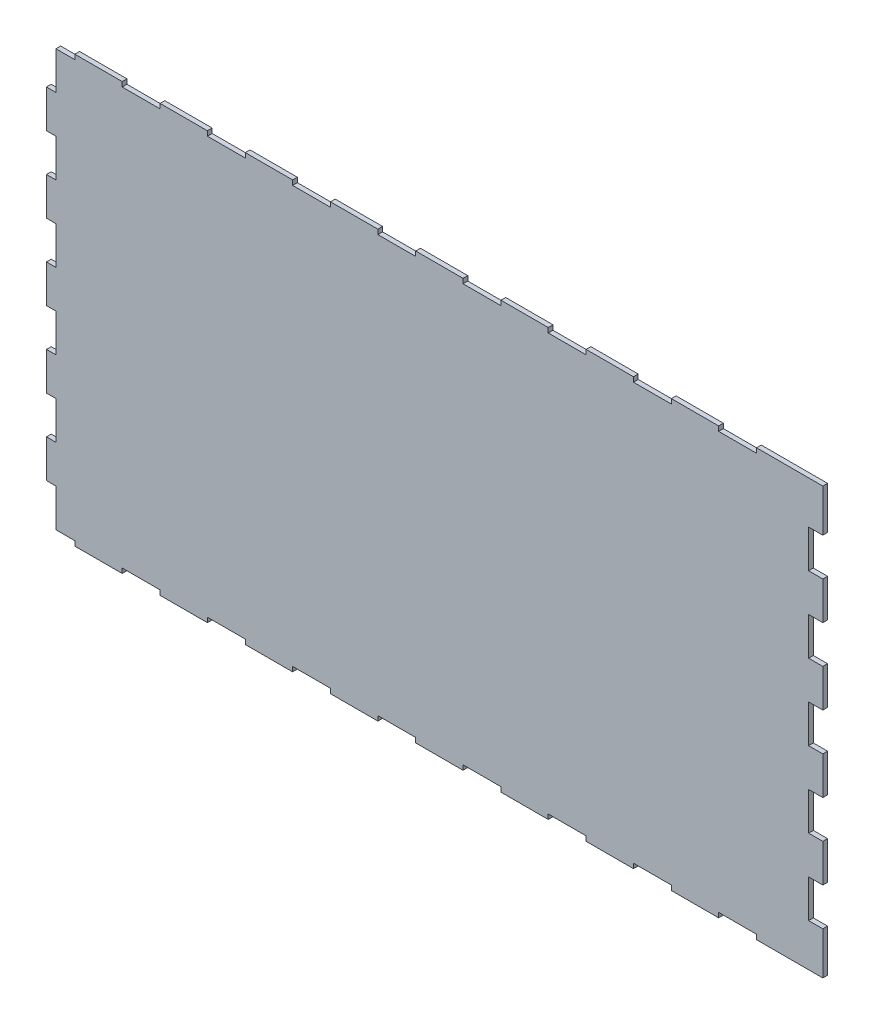
SolidWorks part; units mm, degrees
ref_plane "Front Plane" through (0, 0, 0) normal (0, 0, 1) x (1, 0, 0)
ref_plane "Top Plane" through (0, 0, 0) normal (0, 1, 0) x (1, 0, 0)
ref_plane "Right Plane" through (0, 0, 0) normal (1, 0, 0) x (0, 0, -1)
sketch "Model" plane through (0, 0, 0) normal (0, 0, 1) x (1, 0, 0)
  line L0 (900, 180) -> (885, 180)
  line L1 (885, 140) -> (885, 180)
  line L2 (900, 140) -> (885, 140)
  line L3 (900, 100) -> (900, 140)
  line L4 (900, 100) -> (885, 100)
  line L5 (885, 60) -> (885, 100)
  line L6 (900, 60) -> (885, 60)
  line L7 (900, 20) -> (900, 60)
  line L8 (900, 20) -> (885, 20)
  line L9 (885, -20) -> (885, 20)
  line L10 (900, -20) -> (885, -20)
  line L11 (900, -60) -> (900, -20)
  line L12 (900, -60) -> (885, -60)
  line L13 (885, -100) -> (885, -60)
  line L14 (900, -100) -> (885, -100)
  line L15 (900, -140) -> (900, -100)
  line L16 (900, -140) -> (885, -140)
  line L17 (885, -180) -> (885, -140)
  line L18 (900, -180) -> (885, -180)
  line L19 (900, -225) -> (900, -180)
  line L20 (900, -225) -> (830, -225)
  line L21 (830, -225) -> (830, -220)
  line L22 (830, -220) -> (790, -220)
  line L23 (790, -220) -> (790, -225)
  line L24 (790, -225) -> (740, -225)
  line L25 (740, -225) -> (740, -220)
  line L26 (740, -220) -> (700, -220)
  line L27 (700, -220) -> (700, -225)
  line L28 (700, -225) -> (650, -225)
  line L29 (650, -225) -> (650, -220)
  line L30 (650, -220) -> (610, -220)
  line L31 (610, -220) -> (610, -225)
  line L32 (610, -225) -> (560, -225)
  line L33 (560, -225) -> (560, -220)
  line L34 (560, -220) -> (520, -220)
  line L35 (520, -220) -> (520, -225)
  line L36 (520, -225) -> (470, -225)
  line L37 (470, -225) -> (470, -220)
  line L38 (470, -220) -> (430, -220)
  line L39 (430, -220) -> (430, -225)
  line L40 (430, -225) -> (380, -225)
  line L41 (380, -225) -> (380, -220)
  line L42 (380, -220) -> (340, -220)
  line L43 (340, -220) -> (340, -225)
  line L44 (340, -225) -> (290, -225)
  line L45 (290, -225) -> (290, -220)
  line L46 (290, -220) -> (250, -220)
  line L47 (250, -220) -> (250, -225)
  line L48 (250, -225) -> (200, -225)
  line L49 (200, -225) -> (200, -220)
  line L50 (200, -220) -> (160, -220)
  line L51 (160, -220) -> (160, -225)
  line L52 (160, -225) -> (110, -225)
  line L53 (110, -225) -> (110, -220)
  line L54 (110, -220) -> (70, -220)
  line L55 (70, -220) -> (70, -225)
  line L56 (70, -225) -> (20, -225)
  line L57 (20, -225) -> (20, -220)
  line L58 (20, -220) -> (-20, -220)
  line L59 (-20, -220) -> (-20, -225)
  line L60 (-20, -225) -> (-70, -225)
  line L61 (-70, -225) -> (-70, -220)
  line L62 (-70, -220) -> (-110, -220)
  line L63 (-110, -220) -> (-110, -225)
  line L64 (-110, -225) -> (-160, -225)
  line L65 (-160, -225) -> (-160, -220)
  line L66 (-160, -220) -> (-200, -220)
  line L67 (-200, -220) -> (-200, -225)
  line L68 (-200, -225) -> (-250, -225)
  line L69 (-250, -225) -> (-250, -220)
  line L70 (-250, -220) -> (-290, -220)
  line L71 (-290, -220) -> (-290, -225)
  line L72 (-290, -225) -> (-340, -225)
  line L73 (-340, -225) -> (-340, -220)
  line L74 (-340, -220) -> (-380, -220)
  line L75 (-380, -220) -> (-380, -225)
  line L76 (-380, -225) -> (-430, -225)
  line L77 (-430, -225) -> (-430, -220)
  line L78 (-430, -220) -> (-470, -220)
  line L79 (-470, -220) -> (-470, -225)
  line L80 (-470, -225) -> (-520, -225)
  line L81 (-520, -225) -> (-520, -220)
  line L82 (-520, -220) -> (-560, -220)
  line L83 (-560, -220) -> (-560, -225)
  line L84 (-560, -225) -> (-610, -225)
  line L85 (-610, -225) -> (-610, -220)
  line L86 (-610, -220) -> (-650, -220)
  line L87 (-650, -220) -> (-650, -225)
  line L88 (-650, -225) -> (-700, -225)
  line L89 (-700, -225) -> (-700, -220)
  line L90 (-700, -220) -> (-740, -220)
  line L91 (-740, -220) -> (-740, -225)
  line L92 (-740, -225) -> (-790, -225)
  line L93 (-790, -225) -> (-790, -220)
  line L94 (-790, -220) -> (-830, -220)
  line L95 (-830, -220) -> (-830, -225)
  line L96 (-830, -225) -> (-900, -225)
  line L97 (-900, -225) -> (-900, -180)
  line L98 (-900, -180) -> (-885, -180)
  line L99 (-885, -180) -> (-885, -140)
  line L100 (-900, -140) -> (-885, -140)
  line L101 (-900, -140) -> (-900, -100)
  line L102 (-900, -100) -> (-885, -100)
  line L103 (-885, -100) -> (-885, -60)
  line L104 (-900, -60) -> (-885, -60)
  line L105 (-900, -60) -> (-900, -20)
  line L106 (-900, -20) -> (-885, -20)
  line L107 (-885, -20) -> (-885, 20)
  line L108 (-900, 20) -> (-885, 20)
  line L109 (-900, 20) -> (-900, 60)
  line L110 (-900, 60) -> (-885, 60)
  line L111 (-885, 60) -> (-885, 100)
  line L112 (-900, 100) -> (-885, 100)
  line L113 (-900, 100) -> (-900, 140)
  line L114 (-900, 140) -> (-885, 140)
  line L115 (-885, 140) -> (-885, 180)
  line L116 (-900, 180) -> (-885, 180)
  line L117 (-900, 180) -> (-900, 225)
  line L118 (-830, 225) -> (-900, 225)
  line L119 (-830, 225) -> (-830, 220)
  line L120 (-790, 220) -> (-830, 220)
  line L121 (-790, 225) -> (-790, 220)
  line L122 (-740, 225) -> (-790, 225)
  line L123 (-740, 225) -> (-740, 220)
  line L124 (-700, 220) -> (-740, 220)
  line L125 (-700, 225) -> (-700, 220)
  line L126 (-650, 225) -> (-700, 225)
  line L127 (-650, 225) -> (-650, 220)
  line L128 (-610, 220) -> (-650, 220)
  line L129 (-610, 225) -> (-610, 220)
  line L130 (-560, 225) -> (-610, 225)
  line L131 (-560, 225) -> (-560, 220)
  line L132 (-520, 220) -> (-560, 220)
  line L133 (-520, 225) -> (-520, 220)
  line L134 (-470, 225) -> (-520, 225)
  line L135 (-470, 225) -> (-470, 220)
  line L136 (-430, 220) -> (-470, 220)
  line L137 (-430, 225) -> (-430, 220)
  line L138 (-380, 225) -> (-430, 225)
  line L139 (-380, 225) -> (-380, 220)
  line L140 (-340, 220) -> (-380, 220)
  line L141 (-340, 225) -> (-340, 220)
  line L142 (-290, 225) -> (-340, 225)
  line L143 (-290, 225) -> (-290, 220)
  line L144 (-250, 220) -> (-290, 220)
  line L145 (-250, 225) -> (-250, 220)
  line L146 (-200, 225) -> (-250, 225)
  line L147 (-200, 225) -> (-200, 220)
  line L148 (-160, 220) -> (-200, 220)
  line L149 (-160, 225) -> (-160, 220)
  line L150 (-110, 225) -> (-160, 225)
  line L151 (-110, 225) -> (-110, 220)
  line L152 (-70, 220) -> (-110, 220)
  line L153 (-70, 225) -> (-70, 220)
  line L154 (-20, 225) -> (-70, 225)
  line L155 (-20, 225) -> (-20, 220)
  line L156 (20, 220) -> (-20, 220)
  line L157 (20, 225) -> (20, 220)
  line L158 (70, 225) -> (20, 225)
  line L159 (70, 225) -> (70, 220)
  line L160 (110, 220) -> (70, 220)
  line L161 (110, 225) -> (110, 220)
  line L162 (160, 225) -> (110, 225)
  line L163 (160, 225) -> (160, 220)
  line L164 (200, 220) -> (160, 220)
  line L165 (200, 225) -> (200, 220)
  line L166 (250, 225) -> (200, 225)
  line L167 (250, 225) -> (250, 220)
  line L168 (290, 220) -> (250, 220)
  line L169 (290, 225) -> (290, 220)
  line L170 (340, 225) -> (290, 225)
  line L171 (340, 225) -> (340, 220)
  line L172 (380, 220) -> (340, 220)
  line L173 (380, 225) -> (380, 220)
  line L174 (430, 225) -> (380, 225)
  line L175 (430, 225) -> (430, 220)
  line L176 (470, 220) -> (430, 220)
  line L177 (470, 225) -> (470, 220)
  line L178 (520, 225) -> (470, 225)
  line L179 (520, 225) -> (520, 220)
  line L180 (560, 220) -> (520, 220)
  line L181 (560, 225) -> (560, 220)
  line L182 (610, 225) -> (560, 225)
  line L183 (610, 225) -> (610, 220)
  line L184 (650, 220) -> (610, 220)
  line L185 (650, 225) -> (650, 220)
  line L186 (700, 225) -> (650, 225)
  line L187 (700, 225) -> (700, 220)
  line L188 (740, 220) -> (700, 220)
  line L189 (740, 225) -> (740, 220)
  line L190 (790, 225) -> (740, 225)
  line L191 (790, 225) -> (790, 220)
  line L192 (830, 220) -> (790, 220)
  line L193 (830, 225) -> (830, 220)
  line L194 (900, 225) -> (830, 225)
  line L195 (900, 180) -> (900, 225)
extrude "Boss-Extrude1" add sketch "Model" along normal blind 5
sketch "Sketch1" plane through (0, 0, 5) normal (0, 0, 1) x (1, 0, 0)
  line L0 (90, 220) -> (90, 100)
  line L1 (90, -220) -> (-996.8117, -716.8685)
  line L2 (-996.8117, -716.8685) -> (-1055.8964, 587.3667)
  line L3 (0, 202.5) -> (0, 48.6535) construction
  line L4 (110, 220) -> (70, 220) construction
  line L5 (70, -220) -> (110, -220) construction
  line L6 (-1055.8964, 587.3667) -> (90, 220)
  line L7 (90, 180) -> (80, 180)
  line L8 (90, 180) -> (90, 140)
  line L9 (90, 140) -> (80, 140)
  line L10 (80, 180) -> (80, 140)
  line L13 (90, 60) -> (80, 60)
  line L14 (80, 100) -> (80, 60)
  line L15 (90, 100) -> (80, 100)
  line L16 (90, -20) -> (80, -20)
  line L17 (80, 20) -> (80, -20)
  line L18 (90, 20) -> (80, 20)
  line L19 (90, -100) -> (80, -100)
  line L20 (80, -60) -> (80, -100)
  line L21 (90, -60) -> (80, -60)
  line L22 (90, -180) -> (80, -180)
  line L23 (80, -140) -> (80, -180)
  line L24 (90, -140) -> (80, -140)
  line L25 (90, 60) -> (90, 20)
  line L26 (90, -20) -> (90, -60)
  line L27 (90, -100) -> (90, -140)
  line L28 (90, -180) -> (90, -220)
  dimension "D1" = 40
  dimension "D2" = 40
  dimension "D3" = 10
  dimension "D5" = 40
  dimension "D4" = 5
extrude "Cut-Extrude1" cut sketch "Sketch1" against normal through all contours L3 L6 L2 L1 | L6 L3 L1 L28 L22 L23 L24 L27 L19 L20 L21 L26 L16 L17 L18 L25 L13 L14 L15 L0 L9 L10 L7 region at (-561.9418, -35.87, 5)
